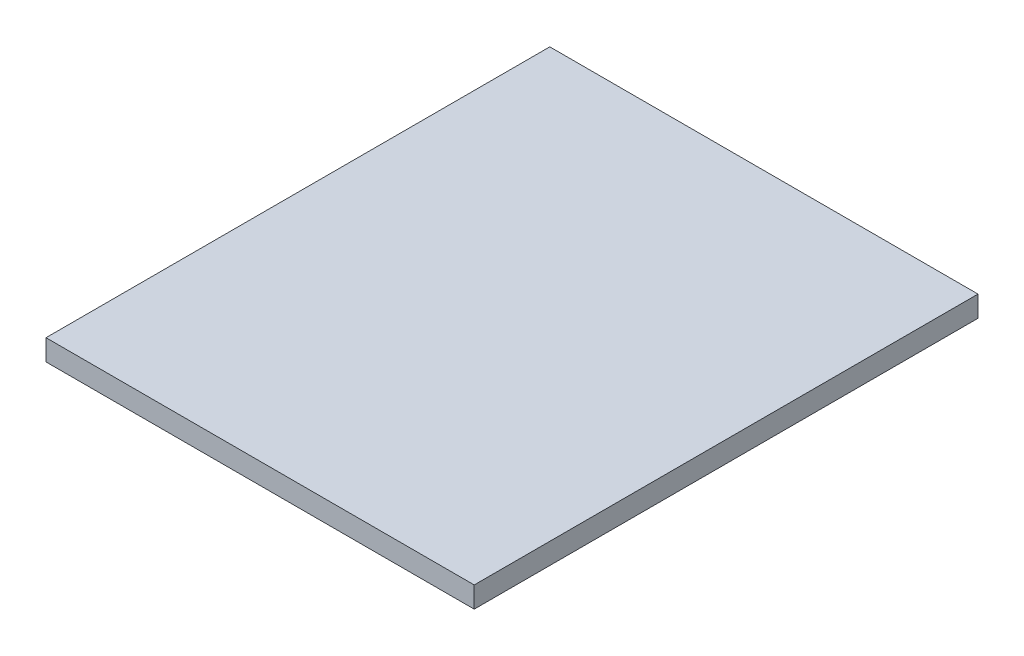
SolidWorks part; units mm, degrees
ref_plane "Front" through (0, 0, 0) normal (0, 0, 1) x (1, 0, 0)
ref_plane "Top" through (0, 0, 0) normal (0, 1, 0) x (1, 0, 0)
ref_plane "Right" through (0, 0, 0) normal (1, 0, 0) x (0, 0, -1)
sketch "Sketch1" plane through (0, 0, 0) normal (0, 1, 0) x (1, 0, 0)
  line L1 (-51, -60) -> (51, -60)
  line L2 (-51, -60) -> (-51, 60)
  line L3 (-51, 60) -> (51, 60)
  line L4 (51, -60) -> (51, 60)
  line L5 (-51, -60) -> (51, 60) construction
  line L6 (-51, 60) -> (51, -60) construction
  point P0 (0, 0)
  dimension "D1" = 102
  dimension "D2" = 120
extrude "Boss-Extrude1" add sketch "Sketch1" along normal blind 5
